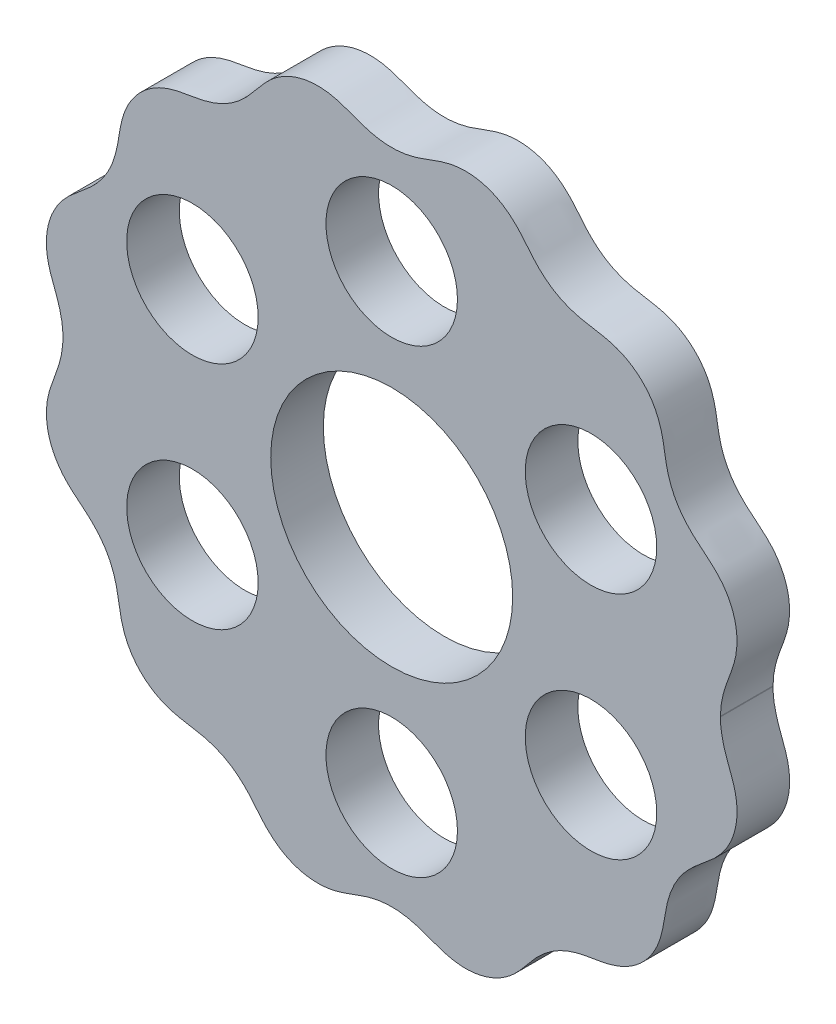
SolidWorks part; units mm, degrees
material "Polylactic Acid (PLA)"
ref_plane "Front Plane" through (0, 0, 0) normal (0, 0, 1) x (1, 0, 0)
ref_plane "Top Plane" through (0, 0, 0) normal (0, 1, 0) x (1, 0, 0)
ref_plane "Right Plane" through (0, 0, 0) normal (1, 0, 0) x (0, 0, -1)
sketch "Sketch3" plane through (0, 0, 0) normal (0, 0, 1) x (1, 0, 0)
  circle A0 centre (0, 0) radius 9.2
  circle A1 centre (0, 0) radius 17.5 construction
  circle A2 centre (0, 17.5) radius 5
  circle A3 centre (15.1554, 8.75) radius 5
  circle A4 centre (15.1554, -8.75) radius 5
  circle A5 centre (0, -17.5) radius 5
  circle A6 centre (-15.1554, -8.75) radius 5
  circle A7 centre (-15.1554, 8.75) radius 5
  spline S0 degree 4 poles (21.1908, 13.4898) (21.2856, 13.2293) (21.5047, 12.7166) (21.9256, 11.9944) (22.6531, 11.1441) (23.6487, 10.2926) (24.8547, 9.373) (25.8136, 8.0448) (26.2513, 6.5807) (26.291, 5.362) (26.1425, 4.3728) (25.9222, 3.637) (25.662, 2.971) (25.4535, 2.4089) (25.3271, 2.03) (25.2348, 1.7101) (25.1694, 1.4518) (25.1138, 1.1915) (25.0684, 0.9287) (25.0339, 0.6638) (25.0136, 0.4392) (25.0034, 0.2182) (24.9998, 0.0511) (24.9998, -0.0519) (25.0027, -0.1861) (25.0086, -0.3317) (25.0175, -0.4711) (25.0292, -0.6041) (25.0438, -0.7358) (25.0613, -0.8682) (25.0866, -1.0342) (25.1223, -1.2324) (25.1717, -1.4616) (25.2379, -1.7216) (25.3315, -2.0435) (25.4377, -2.3615) (25.5528, -2.6764) (25.6953, -3.0525) (25.8373, -3.4288) (26.0075, -3.9196) (26.1691, -4.5364) (26.293, -5.4006) (26.2489, -6.5093) (25.9006, -7.7589) (25.2509, -8.824) (24.5594, -9.5488) (23.8729, -10.1329) (23.242, -10.6335) (22.5405, -11.262) (21.8598, -12.0935) (21.3371, -13.0271) (20.9865, -14.0322) (20.7832, -15.0691) (20.6292, -16.2106) (20.2958, -17.4236) (19.6201, -18.6144) (18.5782, -19.6482) (17.3773, -20.3163) (16.1515, -20.64) (14.7399, -20.8265) (13.4394, -21.1259) (12.2371, -21.7311) (11.2173, -22.5863) (10.5105, -23.3824) (9.8039, -24.3012) (8.9125, -25.2023) (7.7314, -25.9117) (6.3093, -26.2999) (4.9316, -26.2885) (3.7061, -25.9646) (2.6337, -25.523) (1.6267, -25.1818) (0.5814, -24.9891) (-0.4789, -24.9807) (-1.521, -25.1546) (-2.5204, -25.4795) (-3.4192, -25.8479) (-4.2744, -26.1194) (-5.0841, -26.2552) (-5.8272, -26.2778) (-6.7511, -26.1767) (-7.8194, -25.8504) (-8.8645, -25.242) (-9.7745, -24.3376) (-10.489, -23.4094) (-11.1981, -22.6045) (-12.0193, -21.9108) (-12.9507, -21.3713) (-13.9612, -21.0044) (-15.0125, -20.7907) (-16.1735, -20.6366) (-17.4128, -20.3041) (-18.6216, -19.6172) (-19.5352, -18.6909) (-20.1095, -17.7445) (-20.4683, -16.8114) (-20.6693, -15.9295) (-20.8004, -14.9513) (-21.0215, -13.8975) (-21.3995, -12.8918) (-21.9457, -11.9715) (-22.6396, -11.1645) (-23.4354, -10.4692) (-24.3471, -9.7654) (-25.2322, -8.8715) (-25.9257, -7.6947) (-26.3017, -6.2829) (-26.2854, -4.917) (-25.9623, -3.7014) (-25.5242, -2.6362) (-25.1845, -1.6355) (-24.9896, -0.5891) (-24.9797, 0.481) (-25.1578, 1.5405) (-25.4952, 2.5629) (-25.8707, 3.4757) (-26.1355, 4.3406) (-26.2885, 5.3286) (-26.2611, 6.43) (-25.9336, 7.6784) (-25.2377, 8.8666) (-24.345, 9.7676) (-23.427, 10.4756) (-22.627, 11.1764) (-21.9369, 11.9843) (-21.3977, 12.8977) (-21.0267, 13.8865) (-20.8061, 14.9146) (-20.653, 16.0603) (-20.3956, 17.1161) (-19.9569, 18.0284) (-19.3001, 18.9288) (-18.4837, 19.6923) (-17.4358, 20.2946) (-16.1976, 20.6324) (-15.0368, 20.7873) (-13.9849, 20.9979) (-12.9731, 21.361) (-12.0395, 21.8966) (-11.2157, 22.5872) (-10.504, 23.3902) (-9.7903, 24.3186) (-8.8841, 25.2269) (-7.6859, 25.9322) (-6.4273, 26.2622) (-5.3206, 26.2881) (-4.3329, 26.1336) (-3.4683, 25.8679) (-2.5556, 25.4923) (-1.5328, 25.1559) (-0.4731, 24.979) (0.597, 24.9904) (1.6431, 25.1866) (2.6435, 25.5272) (3.7088, 25.9651) (4.9249, 26.2864) (6.2909, 26.3007) (7.702, 25.9226) (8.8779, 25.2273) (9.7704, 24.341) (10.4741, 23.4292) (11.1701, 22.634) (11.978, 21.941) (12.899, 21.3961) (13.9051, 21.0193) (14.9591, 20.7992) (15.9373, 20.6681) (16.819, 20.466) (17.7516, 20.1059) (18.6971, 19.5302) (19.6221, 18.6152) (20.3072, 17.4054) (20.6379, 16.1657) (20.7918, 15.0047) (21.0066, 13.9535) (21.3747, 12.9435) (21.9154, 12.0128) (22.6101, 11.1925) (23.4156, 10.4841) (24.3437, 9.7696) (25.2468, 8.858) (25.9409, 7.6621) (26.2625, 6.4138) (26.2848, 5.4123) (26.1914, 4.7043) (26.0881, 4.2266) (25.9672, 3.8023) (25.8079, 3.3457) (25.6196, 2.8553) (25.4588, 2.4245) (25.3339, 2.0507) (25.2417, 1.7354) (25.1764, 1.4809) (25.1203, 1.2244) (25.0741, 0.9651) (25.0385, 0.7047) (25.017, 0.4825) (25.0053, 0.2643) (25.0004, 0.1004) (24.9996, -0.0012) (25.0018, -0.1656) (25.01, -0.3844) (25.028, -0.6072) (25.0597, -0.8689) (25.1021, -1.1294) (25.1679, -1.4517) (25.266, -1.8346) (25.4047, -2.2742) (25.5863, -2.7686) (25.7756, -3.26) (25.9402, -3.7196) (26.0686, -4.1508) (26.1813, -4.6424) (26.2599, -5.1966) (26.2771, -5.8503) (26.1868, -6.6388) (25.9656, -7.4497) (25.5952, -8.2566) (25.0637, -9.0243) (24.3767, -9.7304) (23.5662, -10.3704) (22.7327, -11.0654) (21.9759, -11.9212) (21.5356, -12.6558) (21.307, -13.1772) (21.208, -13.4432) knots 0 0 0 0 0 0.005467 0.010935 0.016402 0.021869 0.031276 0.040682 0.047884 0.051484 0.055085 0.060328 0.062949 0.065571 0.066882 0.068192 0.069503 0.070814 0.072125 0.073435 0.074746 0.075401 0.076057 0.076717 0.077377 0.078036 0.078696 0.079356 0.080016 0.080676 0.081336 0.082656 0.083975 0.085295 0.086615 0.089254 0.090574 0.091894 0.094534 0.097173 0.100798 0.104424 0.111675 0.118848 0.126022 0.128665 0.131308 0.136594 0.14188 0.147166 0.152358 0.157549 0.16274 0.167931 0.175042 0.182153 0.189327 0.1965 0.201723 0.206946 0.217392 0.222615 0.227838 0.233061 0.238284 0.245457 0.252631 0.259805 0.266978 0.272201 0.277424 0.282647 0.287869 0.29303 0.29819 0.30335 0.30851 0.31216 0.31581 0.319459 0.323109 0.330383 0.337658 0.342925 0.348192 0.35346 0.358727 0.363994 0.369262 0.374529 0.379796 0.387071 0.394345 0.401519 0.405106 0.408692 0.413978 0.419265 0.424551 0.429837 0.435028 0.440219 0.44541 0.450602 0.457712 0.464823 0.471934 0.479045 0.484236 0.489427 0.494619 0.49981 0.505096 0.510382 0.515668 0.520954 0.524541 0.528128 0.535301 0.542475 0.549649 0.554872 0.560094 0.565317 0.57054 0.5757 0.58086 0.58602 0.591181 0.59848 0.60213 0.605779 0.613054 0.620328 0.625595 0.630863 0.63613 0.641397 0.646665 0.651932 0.657199 0.662467 0.669741 0.677015 0.684189 0.687776 0.691363 0.696649 0.701935 0.707221 0.712507 0.717698 0.722889 0.728081 0.733272 0.740383 0.747494 0.754604 0.761715 0.766906 0.772098 0.777289 0.78248 0.787766 0.793052 0.798338 0.803624 0.807211 0.810798 0.817972 0.825246 0.83252 0.837788 0.843055 0.848322 0.85359 0.858857 0.864124 0.869392 0.874659 0.881933 0.889208 0.896232 0.899744 0.9015 0.903256 0.905842 0.908428 0.911014 0.9136 0.914893 0.916186 0.917479 0.918772 0.920065 0.921358 0.922651 0.923297 0.923944 0.924592 0.92524 0.926536 0.927831 0.929127 0.930423 0.931719 0.934311 0.936903 0.939495 0.942087 0.944679 0.946512 0.948345 0.952012 0.955678 0.959345 0.963918 0.968492 0.973065 0.977639 0.983229 0.988819 0.99441 1 1 1 1 1 construction
  spline S1 degree 4 poles (25, 0) (25, -0.0284) (25.0005, -0.0852) (25.0027, -0.1861) (25.0086, -0.3317) (25.0175, -0.4711) (25.0292, -0.6041) (25.0438, -0.7358) (25.0613, -0.8682) (25.0866, -1.0342) (25.1223, -1.2324) (25.1717, -1.4616) (25.2379, -1.7216) (25.3315, -2.0435) (25.4377, -2.3615) (25.5528, -2.6764) (25.6953, -3.0525) (25.8373, -3.4288) (26.0075, -3.9196) (26.1691, -4.5364) (26.293, -5.4006) (26.2489, -6.5093) (25.9006, -7.7589) (25.2509, -8.824) (24.5594, -9.5488) (23.8729, -10.1329) (23.242, -10.6335) (22.5405, -11.262) (21.8598, -12.0935) (21.3371, -13.0271) (20.9865, -14.0322) (20.7832, -15.0691) (20.6292, -16.2106) (20.2958, -17.4236) (19.6201, -18.6144) (18.5782, -19.6482) (17.3773, -20.3163) (16.1515, -20.64) (14.7399, -20.8265) (13.4394, -21.1259) (12.2371, -21.7311) (11.2173, -22.5863) (10.5105, -23.3824) (9.8039, -24.3012) (8.9125, -25.2023) (7.7314, -25.9117) (6.3093, -26.2999) (4.9316, -26.2885) (3.7061, -25.9646) (2.6337, -25.523) (1.6267, -25.1818) (0.5814, -24.9891) (-0.4789, -24.9807) (-1.521, -25.1546) (-2.5204, -25.4795) (-3.4192, -25.8479) (-4.2744, -26.1194) (-5.0841, -26.2552) (-5.8272, -26.2778) (-6.7511, -26.1767) (-7.8194, -25.8504) (-8.8645, -25.242) (-9.7745, -24.3376) (-10.489, -23.4094) (-11.1981, -22.6045) (-12.0193, -21.9108) (-12.9507, -21.3713) (-13.9612, -21.0044) (-15.0125, -20.7907) (-16.1735, -20.6366) (-17.4128, -20.3041) (-18.6216, -19.6172) (-19.5352, -18.6909) (-20.1095, -17.7445) (-20.4683, -16.8114) (-20.6693, -15.9295) (-20.8004, -14.9513) (-21.0215, -13.8975) (-21.3995, -12.8918) (-21.9457, -11.9715) (-22.6396, -11.1645) (-23.4354, -10.4692) (-24.3471, -9.7654) (-25.2322, -8.8715) (-25.9257, -7.6947) (-26.3017, -6.2829) (-26.2854, -4.917) (-25.9623, -3.7014) (-25.5242, -2.6362) (-25.1845, -1.6355) (-24.9896, -0.5891) (-24.9797, 0.481) (-25.1578, 1.5405) (-25.4952, 2.5629) (-25.8707, 3.4757) (-26.1355, 4.3406) (-26.2885, 5.3286) (-26.2611, 6.43) (-25.9336, 7.6784) (-25.2377, 8.8666) (-24.345, 9.7676) (-23.427, 10.4756) (-22.627, 11.1764) (-21.9369, 11.9843) (-21.3977, 12.8977) (-21.0267, 13.8865) (-20.8061, 14.9146) (-20.653, 16.0603) (-20.3956, 17.1161) (-19.9569, 18.0284) (-19.3001, 18.9288) (-18.4837, 19.6923) (-17.4358, 20.2946) (-16.1976, 20.6324) (-15.0368, 20.7873) (-13.9849, 20.9979) (-12.9731, 21.361) (-12.0395, 21.8966) (-11.2157, 22.5872) (-10.504, 23.3902) (-9.7903, 24.3186) (-8.8841, 25.2269) (-7.6859, 25.9322) (-6.4273, 26.2622) (-5.3206, 26.2881) (-4.3329, 26.1336) (-3.4683, 25.8679) (-2.5556, 25.4923) (-1.5328, 25.1559) (-0.4731, 24.979) (0.597, 24.9904) (1.6431, 25.1866) (2.6435, 25.5272) (3.7088, 25.9651) (4.9249, 26.2864) (6.2909, 26.3007) (7.702, 25.9226) (8.8779, 25.2273) (9.7704, 24.341) (10.4741, 23.4292) (11.1701, 22.634) (11.978, 21.941) (12.899, 21.3961) (13.9051, 21.0193) (14.9591, 20.7992) (15.9373, 20.6681) (16.819, 20.466) (17.7516, 20.1059) (18.6971, 19.5302) (19.6221, 18.6152) (20.3072, 17.4054) (20.6379, 16.1657) (20.7918, 15.0047) (21.0066, 13.9535) (21.3747, 12.9435) (21.9154, 12.0128) (22.6101, 11.1925) (23.4156, 10.4841) (24.3437, 9.7696) (25.2468, 8.858) (25.9409, 7.6621) (26.2625, 6.4138) (26.2848, 5.4123) (26.1914, 4.7043) (26.0881, 4.2266) (25.9672, 3.8023) (25.8079, 3.3457) (25.6196, 2.8553) (25.4588, 2.4245) (25.3339, 2.0507) (25.2417, 1.7354) (25.1764, 1.4809) (25.1203, 1.2244) (25.0741, 0.9651) (25.0385, 0.7047) (25.017, 0.4825) (25.0053, 0.2643) (25.0014, 0.1332) (25.0004, 0.0775) (25.0002, 0.0497) knots 0.076057 0.076057 0.076057 0.076057 0.076057 0.076717 0.077377 0.078036 0.078696 0.079356 0.080016 0.080676 0.081336 0.082656 0.083975 0.085295 0.086615 0.089254 0.090574 0.091894 0.094534 0.097173 0.100798 0.104424 0.111675 0.118848 0.126022 0.128665 0.131308 0.136594 0.14188 0.147166 0.152358 0.157549 0.16274 0.167931 0.175042 0.182153 0.189327 0.1965 0.201723 0.206946 0.217392 0.222615 0.227838 0.233061 0.238284 0.245457 0.252631 0.259805 0.266978 0.272201 0.277424 0.282647 0.287869 0.29303 0.29819 0.30335 0.30851 0.31216 0.31581 0.319459 0.323109 0.330383 0.337658 0.342925 0.348192 0.35346 0.358727 0.363994 0.369262 0.374529 0.379796 0.387071 0.394345 0.401519 0.405106 0.408692 0.413978 0.419265 0.424551 0.429837 0.435028 0.440219 0.44541 0.450602 0.457712 0.464823 0.471934 0.479045 0.484236 0.489427 0.494619 0.49981 0.505096 0.510382 0.515668 0.520954 0.524541 0.528128 0.535301 0.542475 0.549649 0.554872 0.560094 0.565317 0.57054 0.5757 0.58086 0.58602 0.591181 0.59848 0.60213 0.605779 0.613054 0.620328 0.625595 0.630863 0.63613 0.641397 0.646665 0.651932 0.657199 0.662467 0.669741 0.677015 0.684189 0.687776 0.691363 0.696649 0.701935 0.707221 0.712507 0.717698 0.722889 0.728081 0.733272 0.740383 0.747494 0.754604 0.761715 0.766906 0.772098 0.777289 0.78248 0.787766 0.793052 0.798338 0.803624 0.807211 0.810798 0.817972 0.825246 0.83252 0.837788 0.843055 0.848322 0.85359 0.858857 0.864124 0.869392 0.874659 0.881933 0.889208 0.896232 0.899744 0.9015 0.903256 0.905842 0.908428 0.911014 0.9136 0.914893 0.916186 0.917479 0.918772 0.920065 0.921358 0.922651 0.923297 0.923944 0.923944 0.923944 0.923944 0.923944
  spline S2 degree 1 poles (25.0002, 0.0497) (25, 0) knots 0 0 1 1
  point P17 (0, 0)
  dimension "D1" = 18.4
  dimension "D2" = 35
  dimension "D3" = 10
  dimension "D4" = 6
extrude "Boss-Extrude2" add sketch "Sketch3" along normal blind 4
